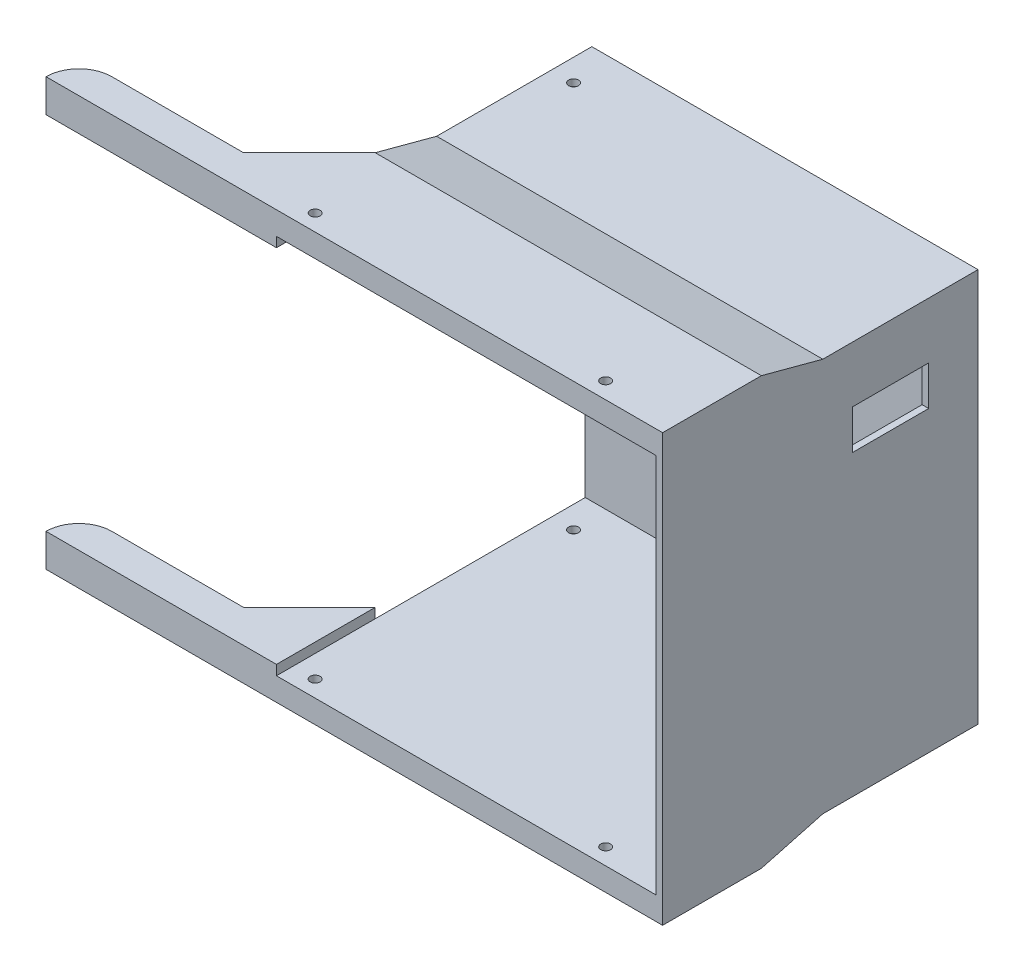
SolidWorks part; units mm, degrees
ref_plane "Top Plane" through (0, 0, 0) normal (0, 0, 1) x (1, 0, 0)
ref_plane "Right Plane" through (0, 0, 0) normal (0, 1, 0) x (1, 0, 0)
ref_plane "Front Plane" through (0, 0, 0) normal (1, 0, 0) x (0, 0, -1)
sketch "Sketch1" plane through (0, 0, 0) normal (0, 0, 1) x (1, 0, 0)
  line L0 (-40, -57.8) -> (75.3, -57.8)
  line L1 (75.3, -57.8) -> (75.3, 57.8)
  line L2 (75.3, 57.8) -> (-40, 57.8)
  line L3 (-40, -59.8) -> (77.3, -59.8)
  line L4 (-40, 57.5) -> (-40, -57.5)
  line L5 (-40, -57.5) -> (75, -57.5)
  line L6 (75, -57.5) -> (75, 57.5)
  line L7 (75, 57.5) -> (-40, 57.5)
  line L9 (-40, -57.5) -> (75, -57.5) construction
  line L10 (75, -57.5) -> (75, 57.5) construction
  line L11 (75, 57.5) -> (-40, 57.5) construction
  line L12 (77.3, -59.8) -> (77.3, 59.8)
  line L13 (77.3, 59.8) -> (-40, 59.8)
  line L14 (-40, 57.8) -> (-40, 59.8)
  line L15 (-40, -59.8) -> (-40, -57.8)
  dimension "D1" = 0
  dimension "D2" = 0.3
  dimension "D3" = 2
extrude "Boss-Extrude1" add sketch "Sketch1" against normal offset from surface (93.8 mm away) 0.3 offset beyond the face yes
sketch "Sketch2" plane through (0, 0, -93.8) normal (0, 0, -1) x (-1, 0, 0)
  line L1 (40, 59.8) -> (-77.3, 59.8)
  line L2 (40, 59.8) -> (40, -59.8)
  line L3 (40, -59.8) -> (-77.3, -59.8)
  line L4 (-77.3, 59.8) -> (-77.3, -59.8)
  circle A0 centre (33.25, -19.1667) radius 1.5 construction
  circle A1 centre (33.25, 19.1667) radius 1.5 construction
  circle A2 centre (33.25, -19.1667) radius 1.5
  circle A3 centre (33.25, 19.1667) radius 1.5
extrude "Boss-Extrude2" add sketch "Sketch2" along normal blind 2
sketch "Sketch5" plane through (0, 59.8, 0) normal (0, 1, 0) x (1, 0, 0)
  line L1 (-40, 0) -> (-110, 0)
  line L2 (-40, 0) -> (-40, 10)
  line L3 (-40, 10) -> (-110, 10)
  line L4 (-110, 0) -> (-110, 10)
  dimension "D1" = 70
  dimension "D2" = 10
extrude "Boss-Extrude3" add sketch "Sketch5" against normal blind 5
sketch "Sketch6" plane through (0, 59.8, 0) normal (0, 1, 0) x (1, 0, 0)
  line L0 (-110, 10) -> (-40, 10)
  line L1 (-40, 10) -> (-110, 10) construction
  line L2 (-40, 10) -> (-40, 30)
  line L4 (0, 0) -> (-110, 0)
  line L5 (-110, 0) -> (-110, 10)
  line L6 (-40, 95.8) -> (-40, 10) construction
  line L7 (77.3, 95.8) -> (77.3, 0) construction
  line L8 (0, 0) -> (77.3, 0)
  line L10 (-40, 30) -> (77.3, 30)
  line L11 (77.3, 0) -> (77.3, 30)
  point P15 (-20.3367, 22.0549)
  point P17 (1.5172, 30)
  dimension "D1" = 30
extrude "Boss-Extrude4" add sketch "Sketch6" along normal blind 5
chamfer "Chamfer1" distance 20 angle 45 1 edges at (-40, 61.3, -10)
sketch "Sketch7" plane through (0, 57.8, 0) normal (0, -1, 0) x (1, 0, 0)
  line L0 (-60, -10) -> (-40, -30) construction
  line L1 (-60, -10) -> (-40, -10) construction
  line L2 (-60, -10) -> (-40, -30)
  line L3 (-60, -10) -> (-40, -10)
  line L4 (-40, -10) -> (-40, -30)
extrude "Boss-Extrude5" add sketch "Sketch7" along normal blind 3
chamfer "Chamfer2" distance 5 angle 75 1 edges at (18.65, 59.8, -30) first distance on face at (18.65, 62.3, -30)
fillet "Fillet1" radius 10 1 edges at (-110, 59.8, -10)
mirror "Mirror5" about plane through (0, 0, 0) normal (0, 1, 0) of bodies 108
sketch "Sketch4" plane through (77.3, 0, 0) normal (1, 0, 0) x (0, 0, -1)
  line L1 (57.6779, 42.75) -> (80.8221, 42.75)
  line L2 (57.6779, 42.75) -> (57.6779, 30.75)
  line L3 (57.6779, 30.75) -> (80.8221, 30.75)
  line L4 (80.8221, 42.75) -> (80.8221, 30.75)
  point P0 (69.25, 30.75)
  point P2 (69.25, 30.75)
  point P7 (57.6779, 30.75)
  point P8 (80.8221, 30.75)
  dimension "D1" = 12
extrude "Cut-Extrude2" cut sketch "Sketch4" against normal through all
sketch "Sketch3" plane through (0, 59.8, 0) normal (0, 1, 0) x (1, 0, 0)
  circle A0 centre (55, 5) radius 1.5 construction
  circle A1 centre (-33.25, 5) radius 1.5 construction
  circle A2 centre (-33.25, 83.5) radius 1.5 construction
  circle A3 centre (55, 5) radius 1.5
  circle A4 centre (-33.25, 5) radius 1.5
  circle A5 centre (-33.25, 83.5) radius 1.5
extrude "Cut-Extrude1" cut sketch "Sketch3" against normal through all both and the other way through all
